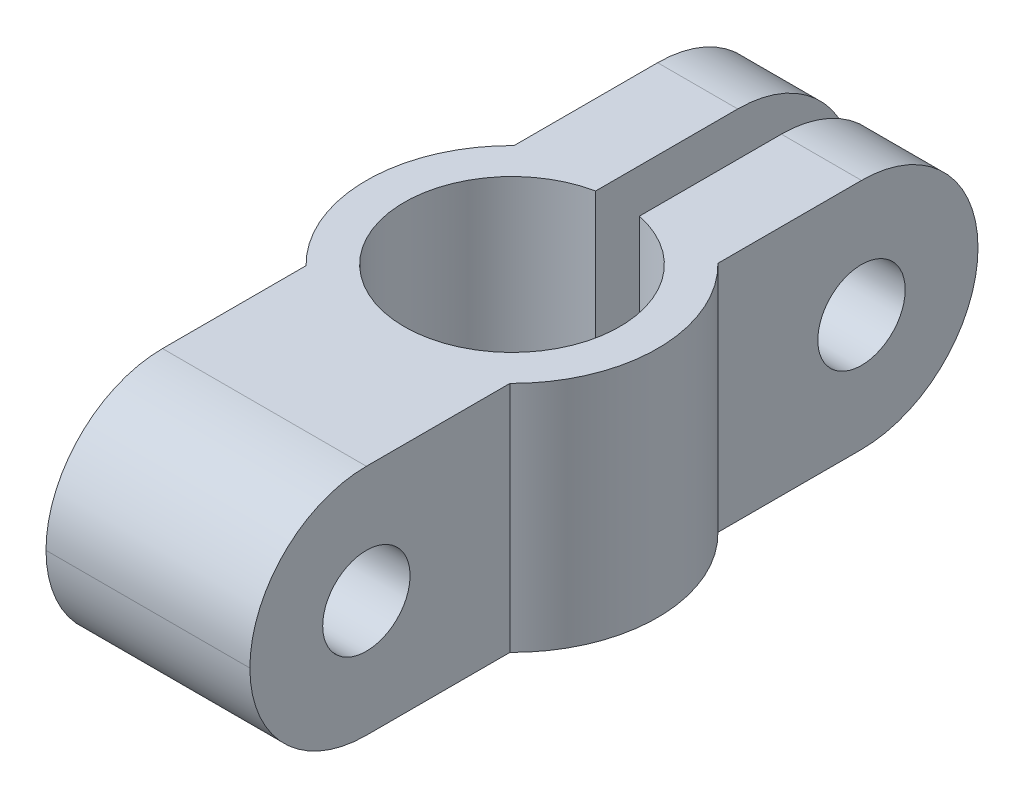
SolidWorks part; units mm, degrees
ref_plane "前视基准面" through (0, 0, 0) normal (0, 0, 1) x (1, 0, 0)
ref_plane "上视基准面" through (0, 0, 0) normal (0, 1, 0) x (1, 0, 0)
ref_plane "右视基准面" through (0, 0, 0) normal (1, 0, 0) x (0, 0, -1)
sketch "草图1" plane through (0, 0, 0) normal (0, 1, 0) x (1, 0, 0)
  line L0 (-3.5, 3.5707) -> (-3.5, 12.5)
  line L1 (3.5, 3.5707) -> (3.5, 12.5)
  line L2 (-3.5, -12.5) -> (3.5, -12.5)
  line L3 (-3.5, -12.5) -> (-3.5, -3.5707)
  line L4 (-3.5, 12.5) -> (3.5, 12.5)
  line L5 (3.5, -12.5) -> (3.5, -3.5707)
  line L6 (-3.5, -12.5) -> (3.5, 12.5) construction
  line L7 (-3.5, 12.5) -> (3.5, -12.5) construction
  arc A0 (-3.5, 3.5707) -> (-3.5, -3.5707) centre (0, 0) ccw
  arc A1 (3.5, -3.5707) -> (3.5, 3.5707) centre (0, 0) ccw
  point P0 (0, 0)
  dimension "D3" = 5
  dimension "D1" = 25
  dimension "D2" = 7
extrude "凸台-拉伸2" add sketch "草图1" along normal blind 8
sketch "草图3" plane through (0, 8, 0) normal (0, 1, 0) x (1, 0, 0)
  circle A0 centre (0, 0) radius 3.7
  dimension "D1" = 7.4
fillet "圆角1" radius 4 2 edges at (0, 0, -12.5) (0, 8, -12.5)
sketch "草图5" plane through (3.5, 0, 0) normal (1, 0, 0) x (0, 0, -1)
  circle A0 centre (8.5, 4) radius 1.5
extrude "切除-拉伸1" cut sketch "草图5" against normal through all
extrude "切除-拉伸2" cut sketch "草图3" against normal through all
fillet "圆角3" radius 4 2 edges at (0, 8, 12.5) (0, 0, 12.5)
sketch "草图6" plane through (-3.5, 0, 0) normal (-1, 0, 0) x (0, 0, 1)
  circle A0 centre (8.5, 4) radius 1.5
extrude "切除-拉伸3" cut sketch "草图6" against normal through all
sketch "草图7" plane through (0, 8, 0) normal (0, 1, 0) x (1, 0, 0)
  line L2 (-0.75, 3.5) -> (0.75, 3.5)
  line L3 (0.75, 3.5) -> (0.75, 14.6057)
  line L4 (0.75, 14.6057) -> (-0.75, 14.6057)
  line L5 (-0.75, 14.6057) -> (-0.75, 3.5)
extrude "切除-拉伸5" cut sketch "草图7" against normal blind 10
